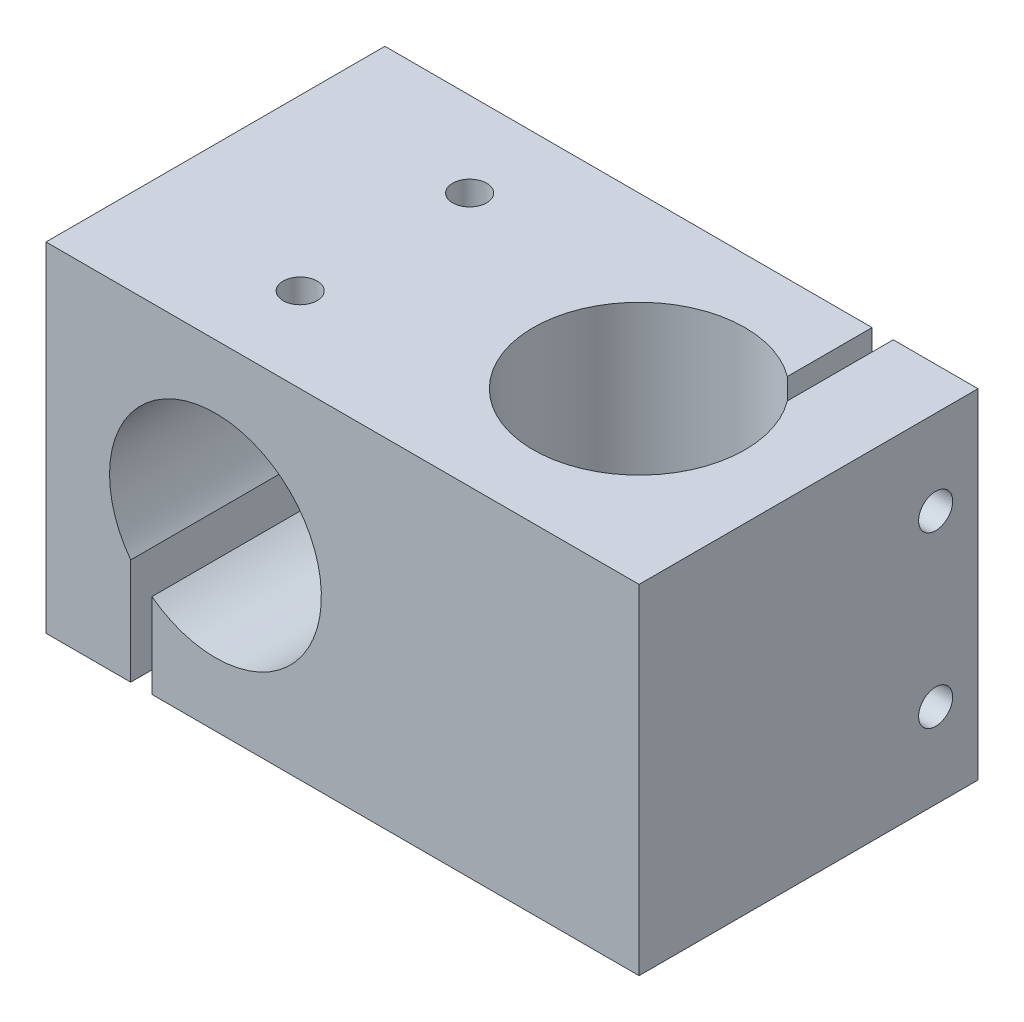
SolidWorks part; units mm, degrees
ref_plane "Front" through (0, 0, 0) normal (0, 0, 1) x (1, 0, 0)
ref_plane "Top" through (0, 0, 0) normal (0, 1, 0) x (1, 0, 0)
ref_plane "Right" through (0, 0, 0) normal (1, 0, 0) x (0, 0, -1)
sketch "Sketch1" plane through (0, 0, 0) normal (0, 1, 0) x (1, 0, 0)
  line L1 (-44.45, -25.4) -> (44.45, -25.4)
  line L2 (-44.45, -25.4) -> (-44.45, 25.4)
  line L3 (-44.45, 25.4) -> (44.45, 25.4)
  line L4 (44.45, -25.4) -> (44.45, 25.4)
  line L5 (-44.45, -25.4) -> (44.45, 25.4) construction
  line L6 (-44.45, 25.4) -> (44.45, -25.4) construction
  point P0 (0, 0)
  dimension "D1" = 50.8
  dimension "D2" = 88.9
extrude "Boss-Extrude1" add sketch "Sketch1" along normal mid plane 50.8 contours L3 L4 L1 L2
sketch "Sketch2" plane through (0, 25.4, 0) normal (0, 1, 0) x (1, 0, 0)
  line L0 (-50, 0) -> (50, 0) construction
  line L1 (44.45, -25.4) -> (44.45, 25.4) construction
  circle A0 centre (19.05, 0) radius 15.875
  dimension "D1" = 31.75
  dimension "D2" = 25.4
extrude "Cut-Extrude1" cut sketch "Sketch2" against normal up to next
sketch "Sketch3" plane through (0, 25.4, 0) normal (0, 1, 0) x (1, 0, 0)
  line L0 (-44.45, 25.4) -> (44.45, 25.4) construction
  line L1 (28.575, 9.525) -> (31.75, 9.525)
  line L2 (28.575, 9.525) -> (28.575, 25.4)
  line L3 (28.575, 25.4) -> (31.75, 25.4)
  line L4 (31.75, 9.525) -> (31.75, 25.4)
  line L5 (28.575, 9.525) -> (31.75, 25.4) construction
  line L6 (28.575, 25.4) -> (31.75, 9.525) construction
  line L7 (44.45, -25.4) -> (44.45, 25.4) construction
  circle A0 centre (19.05, 0) radius 15.875 construction
  point P0 (30.1625, 17.4625)
  dimension "D1" = 12.7
  dimension "D2" = 3.175
extrude "Cut-Extrude4" cut sketch "Sketch3" against normal blind 50.8 contours L2 L3 L4 L1
sketch "Sketch4" plane through (44.45, 0, 0) normal (1, 0, 0) x (0, 0, -1)
  line L0 (19.05, 12.7) -> (19.05, -12.7) construction
  line L1 (50, 0) -> (-50, 0) construction
  line L2 (25.4, 25.4) -> (25.4, -25.4) construction
  point P0 (19.05, 12.7)
  point P1 (19.05, -12.7)
  point P4 (19.05, 0)
  dimension "D1" = 25.4
  dimension "D2" = 6.35
hole_wizard "1/4-20 Tapped Hole1" positions "Sketch5" profile "Sketch6" tap size "1/4-20" standard "ANSI Inch"
sketch "Sketch5" plane through (44.45, 0, 0) normal (1, 0, 0) x (0, 0, -1)
  point P0 (19.05, 12.7)
  point P3 (19.05, -12.7)
sketch "Sketch6" plane through (44.45, 12.7, -19.05) normal (0, 1, 0) x (0, 0, -1)
  line L0 (0, 0) -> (0, 26.9338)
  line L1 (0, 26.9338) -> (2.5527, 25.4)
  line L2 (2.5527, 25.4) -> (2.5527, 0)
  line L5 (2.5527, 0) -> (0, 0)
  line L10 (0, 26.9338) -> (-2.5527, 25.4) construction
  line L11 (0, -6.35) -> (0, 107.95) construction
  dimension "Tap Drill Dia." = 5.1054
  dimension "Tap Drill Depth" = 25.4
  dimension "Drill Angle" = 118
sketch "Sketch7" plane through (0, 0, 25.4) normal (0, 0, 1) x (1, 0, 0)
  line L0 (50, 0) -> (-50, 0) construction
  line L1 (-44.45, 25.4) -> (-44.45, -25.4) construction
  circle A0 centre (-19.05, 0) radius 15.875
  dimension "D1" = 31.75
  dimension "D2" = 25.4
extrude "Cut-Extrude5" cut sketch "Sketch7" against normal blind 50.8
sketch "Sketch8" plane through (0, 0, 25.4) normal (0, 0, 1) x (1, 0, 0)
  line L0 (-44.45, -25.4) -> (44.45, -25.4) construction
  line L1 (-31.75, -25.4) -> (-28.575, -25.4)
  line L2 (-31.75, -25.4) -> (-31.75, -9.525)
  line L3 (-31.75, -9.525) -> (-28.575, -9.525)
  line L4 (-28.575, -25.4) -> (-28.575, -9.525)
  line L5 (-31.75, -25.4) -> (-28.575, -9.525) construction
  line L6 (-31.75, -9.525) -> (-28.575, -25.4) construction
  line L7 (-44.45, 25.4) -> (-44.45, -25.4) construction
  circle A0 centre (-19.05, 0) radius 15.875 construction
  point P0 (-30.1625, -17.4625)
  dimension "D1" = 12.7
  dimension "D2" = 3.175
extrude "Cut-Extrude6" cut sketch "Sketch8" against normal blind 50.8
sketch "Sketch9" plane through (-44.45, 0, 0) normal (-1, 0, 0) x (0, 0, 1)
  line L0 (-12.7, -19.05) -> (12.7, -19.05) construction
  line L1 (0, -50) -> (0, 50) construction
  line L2 (25.4, -25.4) -> (-25.4, -25.4) construction
  point P0 (-12.7, -19.05)
  point P1 (12.7, -19.05)
  point P4 (0, -19.05)
  dimension "D1" = 25.4
  dimension "D2" = 6.35
hole_wizard "1/4-20 Tapped Hole2" positions "Sketch10" profile "Sketch11" tap size "1/4-20" standard "ANSI Inch"
sketch "Sketch10" plane through (-44.45, 0, 0) normal (-1, 0, 0) x (0, 0, 1)
  point P0 (-12.7, -19.05)
  point P3 (12.7, -19.05)
sketch "Sketch11" plane through (-44.45, -19.05, -12.7) normal (0, 1, 0) x (0, 0, 1)
  line L0 (0, 0) -> (0, 26.9338)
  line L1 (0, 26.9338) -> (2.5527, 25.4)
  line L2 (2.5527, 25.4) -> (2.5527, 0)
  line L5 (2.5527, 0) -> (0, 0)
  line L10 (0, 26.9338) -> (-2.5527, 25.4) construction
  line L11 (0, -6.35) -> (0, 107.95) construction
  dimension "Tap Drill Dia." = 5.1054
  dimension "Tap Drill Depth" = 25.4
  dimension "Drill Angle" = 118
sketch "Sketch12" plane through (0, 25.4, 0) normal (0, 1, 0) x (1, 0, 0)
  line L0 (-19.05, 12.7) -> (-19.05, -12.7) construction
  line L1 (-50, 0) -> (50, 0) construction
  line L2 (-44.45, -25.4) -> (-44.45, 25.4) construction
  point P0 (-19.05, 12.7)
  point P1 (-19.05, -12.7)
  point P4 (-19.05, 0)
  dimension "D1" = 25.4
  dimension "D2" = 25.4
hole_wizard "1/4-20 Tapped Hole3" positions "3DSketch1" profile "Sketch13" tap size "1/4-20" standard "ANSI Inch"
sketch3d "3DSketch1"
  point P0 (-19.05, 25.4, -12.7)
  point P3 (-19.05, 25.4, 12.7)
sketch "Sketch13" plane through (-19.05, 25.4, -12.7) normal (1, 0, 0) x (0, 0, 1)
  line L0 (0, 0) -> (0, 26.9338)
  line L1 (0, 26.9338) -> (2.5527, 25.4)
  line L2 (2.5527, 25.4) -> (2.5527, 0)
  line L5 (2.5527, 0) -> (0, 0)
  line L10 (0, 26.9338) -> (-2.5527, 25.4) construction
  line L11 (0, -6.35) -> (0, 107.95) construction
  dimension "Tap Drill Dia." = 5.1054
  dimension "Tap Drill Depth" = 25.4
  dimension "Drill Angle" = 118
